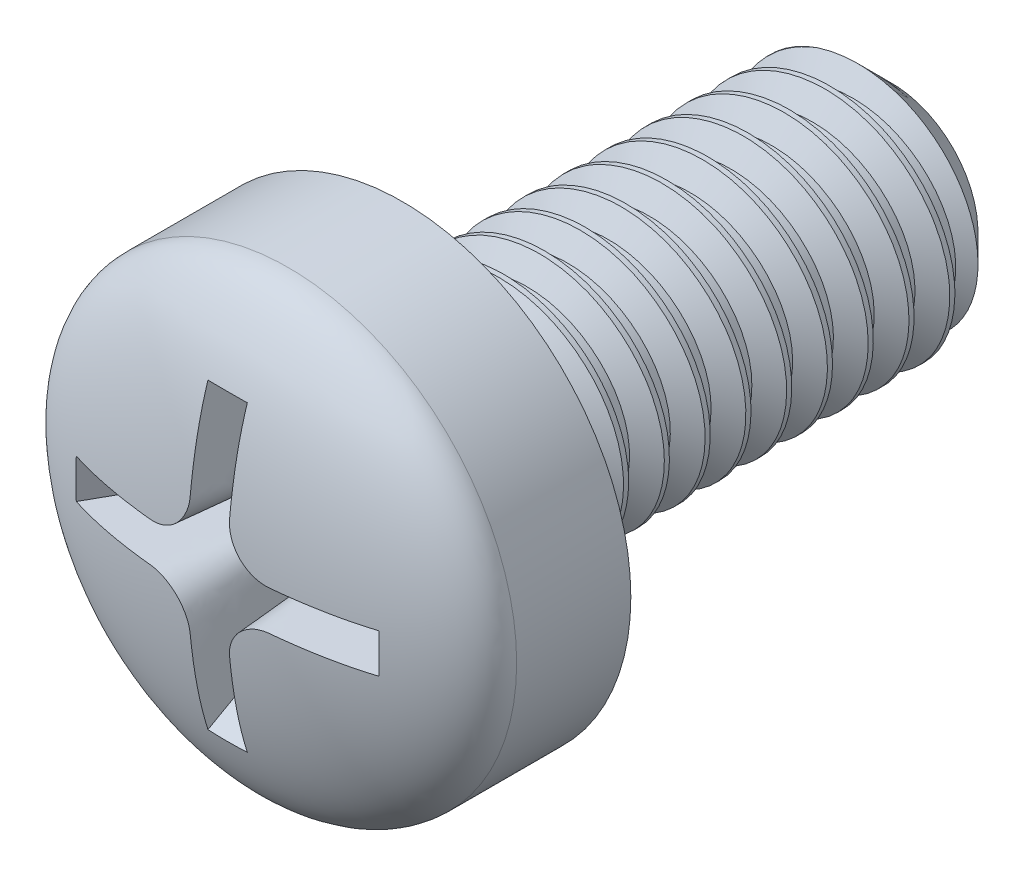
SolidWorks part; units mm, degrees
ref_plane "Front Plane" through (0, 0, 0) normal (0, 0, 1) x (1, 0, 0)
ref_plane "Top Plane" through (0, 0, 0) normal (0, 1, 0) x (1, 0, 0)
ref_plane "Right Plane" through (0, 0, 0) normal (1, 0, 0) x (0, 0, -1)
ref_plane "ThreadStarts" through (0, 0, -0.5) normal (0, 0, 1) x (1, 0, 0)
ref_plane "CapPlane" through (0, 0, 2.4) normal (0, 0, 1) x (1, 0, 0)
sketch "Blank_Profile" plane through (0, 0, 0) normal (0, 1, 0) x (0, 0, -1)
  line L6 (6, 0) -> (0, 0)
  line L7 (6, -1.057) -> (6, 0)
  line L8 (0, 0) -> (0, -1.2194)
  line L9 (5.567, -1.49) -> (6, -1.057)
  line L10 (0.7706, -1.49) -> (5.567, -1.49)
  line L11 (0.5, -1.2194) -> (0.7706, -1.49)
  line L12 (0, -1.2194) -> (0.5, -1.2194)
  dimension "Length" = 6
  dimension "D2" = 1.2194
  dimension "D3" = 1.057
  dimension "D4" = 45
  dimension "D5" = 0.5
  dimension "D6" = 45
  dimension "D7" = 1.49
sketch "HeadCirc" plane through (0, 0, 0) normal (0, 0, 1) x (1, 0, 0)
  circle A0 centre (0, 0) radius 2.8
  dimension "D1" = 5.6
extrude "Head" add sketch "HeadCirc" along normal blind 1.4
revolve "Revolve_Blank" add sketch "Blank_Profile" angle 360 about L6
dome "Dome1" faces to dome 1 distance 1 reverse direction no elliptical dome yes face at (2.8, 0, 1.4) parameters "D1"=1
fillet "Fillet1" radius 0.5 1 edges at (1.2194, 0, 0)
sketch "ThreadCut" plane through (0, 0, 0) normal (0, 1, 0) x (1, 0, 0)
  line L0 (1.1111, 0.5) -> (1.74, 0.5) construction
  line L1 (-3.08, 0) -> (3.08, 0) construction
  line L2 (1.2194, 0.4375) -> (1.49, 0.2813)
  line L3 (1.49, 0.2813) -> (1.74, 0.2813)
  line L4 (1.74, 0.2813) -> (1.74, 0.7187)
  line L5 (1.2194, 0.5625) -> (1.49, 0.7187)
  line L6 (1.49, 0.7187) -> (1.74, 0.7187)
  line L7 (1.5441, 0.25) -> (1.1111, 0.5) construction
  line L8 (1.2194, 0.4375) -> (1.2194, 0.5625)
  line L10 (0, -3.08) -> (0, 3.08) construction
  line L12 (0, -0.2288) -> (0, 0.7371) construction
  dimension "D4" = 1.49
  dimension "D5" = 0.1082
  dimension "D7" = 0.0541
  dimension "D6" = 0.433
  dimension "D1" = 60
  dimension "D2" = 0.5
  dimension "D3" = 0.25
  dimension "D8" = 1.2194
sketch "Sketch4" plane through (0, 0, -0.5) normal (0, 0, 1) x (1, 0, 0)
  circle A0 centre (0, 0) radius 1.49
  dimension "D1" = 2.98
curve "ThreadGroove" pitch 0.5 height 6 radius 1.49 centre (0, 0, -0.5) axis (0, 0, -1) start towards (1, 0, 0)
sweep "CutThreads" cut profiles "ThreadCut" path "ThreadGroove"
sketch "TopCross" plane through (0, 0, 2.4) normal (0, 0, 1) x (1, 0, 0)
  line L0 (0, 2.9503) -> (0, -2.9415) construction
  line L1 (-0.2413, 2) -> (0.2413, 2)
  line L2 (-0.2413, 2) -> (-0.2413, 0.7413)
  line L3 (0, -3.08) -> (0, 3.08) construction
  line L4 (0.2413, 2) -> (0.2413, 0.7413)
  line L5 (0.7413, 0.2413) -> (2, 0.2413)
  line L6 (-3.0117, 0) -> (2.9678, 0) construction
  line L7 (0.7413, -0.2413) -> (2, -0.2413)
  line L8 (2, 0.2413) -> (2, -0.2413)
  line L9 (3.08, 0) -> (-3.08, 0) construction
  line L10 (0.2413, -0.7413) -> (0.2413, -2)
  line L11 (0.2413, -2) -> (-0.2413, -2)
  line L12 (-0.2413, -0.7413) -> (-0.2413, -2)
  line L13 (-0.7413, -0.2413) -> (-2, -0.2413)
  line L15 (-0.7413, 0.2413) -> (-2, 0.2413)
  line L16 (-2, -0.2413) -> (-2, 0.2413)
  arc A0 (-0.2413, 0.7413) -> (-0.7413, 0.2413) centre (-0.7413, 0.7413) cw
  arc A1 (0.7413, 0.2413) -> (0.2413, 0.7413) centre (0.7413, 0.7413) cw
  arc A2 (0.2413, -0.7413) -> (0.7413, -0.2413) centre (0.7413, -0.7413) cw
  arc A3 (-0.7413, -0.2413) -> (-0.2413, -0.7413) centre (-0.7413, -0.7413) cw
  dimension "D1" = 0.5
  dimension "D2" = 4
  dimension "D3" = 4
  dimension "D4" = 0.4826
  dimension "D5" = 0.4826
sketch "Recess_Cross" plane through (0, 0, 0) normal (0, 0, 1) x (1, 0, 0)
  line L0 (0, 2.9503) -> (0, -2.9415) construction
  line L1 (-0.2413, 0.65) -> (0.2413, 0.65)
  line L2 (-0.2413, 0.65) -> (-0.2413, 0.2913)
  line L3 (3.08, 0) -> (-3.08, 0) construction
  line L4 (0.2413, 0.65) -> (0.2413, 0.2913)
  line L5 (0.2913, 0.2413) -> (0.65, 0.2413)
  line L6 (-3.0117, 0) -> (2.9678, 0) construction
  line L7 (0.2913, -0.2413) -> (0.65, -0.2413)
  line L8 (0.65, 0.2413) -> (0.65, -0.2413)
  line L9 (0, -3.08) -> (0, 3.08) construction
  line L10 (0.2413, -0.2913) -> (0.2413, -0.65)
  line L11 (0.2413, -0.65) -> (-0.2413, -0.65)
  line L12 (-0.2413, -0.2913) -> (-0.2413, -0.65)
  line L13 (-0.2913, -0.2413) -> (-0.65, -0.2413)
  line L15 (-0.2913, 0.2413) -> (-0.65, 0.2413)
  line L16 (-0.65, -0.2413) -> (-0.65, 0.2413)
  arc A0 (-0.2413, 0.2913) -> (-0.2913, 0.2413) centre (-0.2913, 0.2913) cw
  arc A1 (0.2913, 0.2413) -> (0.2413, 0.2913) centre (0.2913, 0.2913) cw
  arc A2 (0.2413, -0.2913) -> (0.2913, -0.2413) centre (0.2913, -0.2913) cw
  arc A3 (-0.2913, -0.2413) -> (-0.2413, -0.2913) centre (-0.2913, -0.2913) cw
  dimension "D1" = 0.05
  dimension "D2" = 1.3
  dimension "D3" = 0.4826
  dimension "D4" = 0.4826
  dimension "D5" = 1.3
loft "DriverSlot" cut profiles "TopCross", "Recess_Cross" connector at (-0.2413, 2, 2.4) connector at (-0.2413, 0.65, 0)
